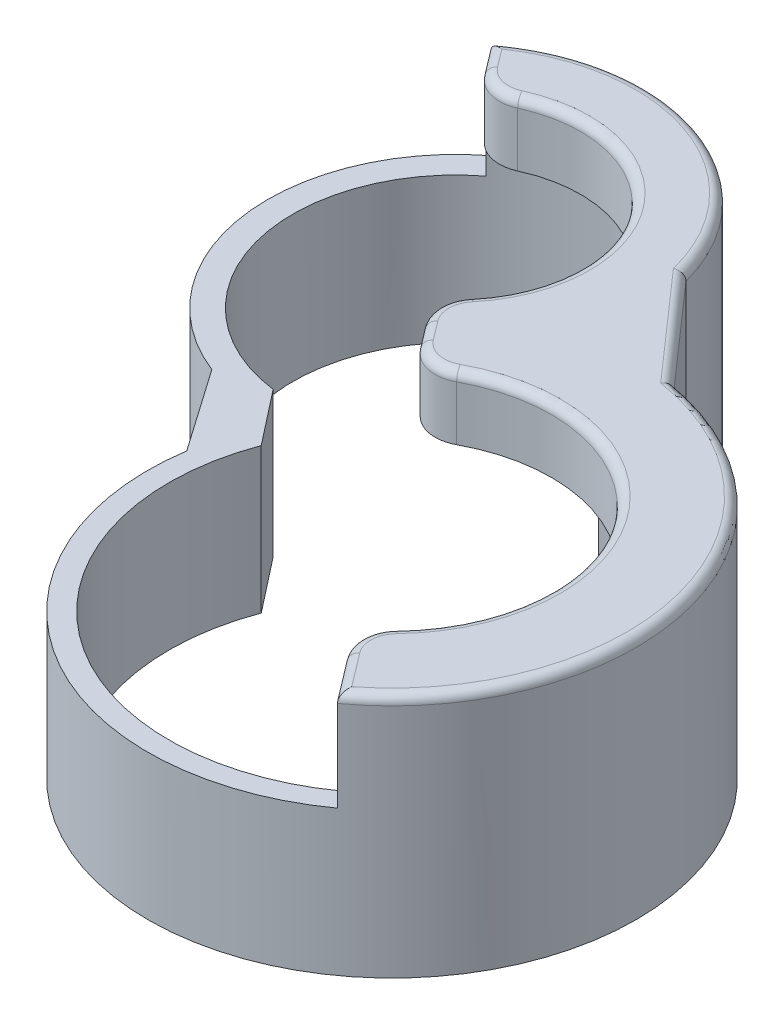
SolidWorks part; units mm, degrees
note: The reader was unsure of these and kept them because the rebuilt part matched: shared geometry of "Sketch1<8>".
ref_plane "Front Plane" through (0, 0, 0) normal (0, 0, 1) x (1, 0, 0)
ref_plane "Top Plane" through (0, 0, 0) normal (0, 1, 0) x (1, 0, 0)
ref_plane "Right Plane" through (0, 0, 0) normal (1, 0, 0) x (0, 0, -1)
sketch "Sketch1" plane through (0, 0, 0) normal (0, 1, 0) x (1, 0, 0)
  circle A0 centre (22.4937, 43.6292) radius 8.15
  circle A9 centre (35.203, 27.3848) radius 11.45
  circle A10 centre (35.203, 27.3848) radius 12.3
  circle A16 centre (22.4937, 43.6292) radius 9
  circle A20 centre (22.4937, 43.6292) radius 5
  circle A21 centre (35.203, 27.3848) radius 5
  dimension "D1" = 16.3
  dimension "D6" = 22.9
  dimension "D7" = 24.6
  dimension "D12" = 18
extrude "Boss-Extrude4" add sketch "Sketch1" along normal blind 59 contours A10 A16 | A10 A16 A0 | A16 A10 A9
extrude "Boss-Extrude17" add sketch "Sketch1<8>" along normal blind 10 draft 1
sketch "Sketch1<8>" plane through (0, 0, 0) normal (0, 1, 0) x (1, 0, 0) same geometry as "Sketch1"
sketch "Sketch12" plane through (0, 0, 0) normal (0, -1, 0) x (-1, 0, 0)
  line L1 (-34.9775, 38.8326) -> (-30.6051, 44.4212)
  line L2 (-24.3049, 30.8971) -> (-20.5326, 35.7186)
  circle A0 centre (-35.203, 27.3848) radius 3
  circle A1 centre (-22.4937, 43.6292) radius 3
  circle A2 centre (-35.203, 27.3848) radius 11.45 construction
  circle A3 centre (-35.203, 27.3848) radius 5 construction
  circle A4 centre (-22.4937, 43.6292) radius 8.15 construction
  arc A5 (-25.731, 35.2316) -> (-29.8657, 38.4665) centre (-22.4937, 43.6292) ccw construction
  arc A6 (-20.5326, 35.7186) -> (-30.6051, 44.4212) centre (-22.4937, 43.6292) cw
  arc A7 (-34.9775, 38.8326) -> (-24.3049, 30.8971) centre (-35.203, 27.3848) cw
extrude "Boss-Extrude19" add sketch "Sketch12" against normal blind 59 contours A7 L2 A6 L1
sketch "Sketch17" plane through (0, 0, 0) normal (0, -1, 0) x (1, 0, 0)
  line L0 (23.6821, -31.6931) -> (21.3254, -34.7053)
  line L1 (23.6821, -31.6931) -> (21.3254, -34.7053) construction
  circle A0 centre (35.203, -27.3848) radius 12.3
  circle A1 centre (22.4937, -43.6292) radius 9
  circle M6 centre (35.203, -27.3848) radius 11.45
  circle M7 centre (22.4937, -43.6292) radius 8.15
extrude "Boss-Extrude20" add sketch "Sketch17" against normal blind 3 contours M6 | M7
sketch "Sketch19" plane through (0, 0, 0) normal (0, -1, 0) x (-1, 0, 0)
  circle A0 centre (-35.203, 27.3848) radius 3.2
  circle A1 centre (-22.4937, 43.6292) radius 3.2
  arc A2 (-34.3348, 39.6541) -> (-23.6821, 31.6931) centre (-35.203, 27.3848) ccw construction
  arc A3 (-21.3254, 34.7053) -> (-31.4874, 43.2935) centre (-22.4937, 43.6292) ccw construction
extrude "Cut-Extrude5" cut sketch "Sketch19" against normal blind 10 contours A0 | A1
sketch "Sketch21" plane through (0, 59, 0) normal (0, 1, 0) x (1, 0, 0)
  line L0 (22.4937, 43.6292) -> (35.203, 27.3848) construction
  line L1 (35.203, 27.3848) -> (42.5661, 17.5322) construction
  line L2 (42.5661, 17.5322) -> (17.0125, 50.7675) construction
  line L3 (17.0125, 50.7675) -> (42.5661, 17.5322)
  arc A0 (23.6821, 31.6931) -> (34.3348, 39.6541) centre (35.203, 27.3848) ccw construction
  arc A1 (31.4874, 43.2935) -> (21.3254, 34.7053) centre (22.4937, 43.6292) ccw construction
  circle A2 centre (22.4937, 43.6292) radius 5.0208
  circle A3 centre (35.203, 27.3848) radius 8.7909
sketch "Sketch23" plane through (0, 59, 0) normal (0, 1, 0) x (1, 0, 0)
  line L0 (32.547, 46.256) -> (37.4683, 40.6622)
  line L1 (21.8828, 29.3833) -> (18.69, 33.9596)
  circle A0 centre (35.203, 27.3848) radius 13.4692
  circle A1 centre (22.4937, 43.6292) radius 10.3908
  point P8 (0, 0)
  point P9 (21.8828, 29.3833)
  point P10 (18.69, 33.9596)
  point P11 (0, 0)
  line M5 (21.3254, 34.7053) -> (23.6821, 31.6931)
  arc M6 (23.6821, 31.6931) -> (34.3348, 39.6541) centre (35.203, 27.3848) ccw
  line M7 (34.3348, 39.6541) -> (31.4874, 43.2935)
  arc M8 (31.4874, 43.2935) -> (21.3254, 34.7053) centre (22.4937, 43.6292) ccw
extrude "Boss-Extrude21" add sketch "Sketch23" along normal blind 10 separate body contours A1 L1 A0 M5 | A1 M7 M5 M8 | A1 A0 L0 M7 | A0 M7 M6 M5
sketch "Sketch24" plane through (0, 69, 0) normal (0, 1, 0) x (1, 0, 0)
  line L0 (34.0133, 36.0949) -> (28.919, 41.1893)
  line L1 (18.309, 49.0813) -> (16.1671, 51.8719)
  line L2 (17.0125, 50.7675) -> (42.5661, 17.5322) construction
  line L3 (40.427, 20.3144) -> (43.0995, 16.4731)
  circle A0 centre (22.4937, 43.6292) radius 6.8729
  circle A1 centre (35.203, 27.3848) radius 0.1682
  circle A2 centre (35.203, 27.3848) radius 8.7909
  arc A3 (32.547, 46.256) -> (18.69, 33.9596) centre (22.4937, 43.6292) ccw construction
  arc A4 (21.8828, 29.3833) -> (37.4683, 40.6622) centre (35.203, 27.3848) ccw construction
sketch "Sketch35" plane through (0, 0, 0) normal (0, -1, 0) x (1, 0, 0)
  line L0 (21.3254, -34.7053) -> (23.6821, -31.6931)
  line L1 (34.3348, -39.6541) -> (31.4874, -43.2935)
  arc A0 (23.6821, -31.6931) -> (34.3348, -39.6541) centre (35.203, -27.3848) cw
  arc A1 (31.4874, -43.2935) -> (21.3254, -34.7053) centre (22.4937, -43.6292) cw
extrude "Cut-Extrude8" cut sketch "Sketch35" against normal blind 66
sketch "Sketch36" plane through (0, 69, 0) normal (0, 1, 0) x (1, 0, 0)
  line L0 (43.0995, 16.4731) -> (16.1671, 51.8719)
  line L1 (18.69, 33.9596) -> (21.8828, 29.3833)
  arc A0 (16.1671, 51.8719) -> (18.69, 33.9596) centre (22.4937, 43.6292) ccw
  arc A1 (21.8828, 29.3833) -> (43.0995, 16.4731) centre (35.203, 27.3848) ccw
extrude "Cut-Extrude9" cut sketch "Sketch36" against normal blind 2
sketch "Sketch37" plane through (0, 69, 0) normal (0, 1, 0) x (1, 0, 0)
  line L0 (43.0995, 16.4731) -> (16.1671, 51.8719)
  line L1 (32.547, 46.256) -> (37.4683, 40.6622)
  arc A0 (32.547, 46.256) -> (16.5974, 52.185) centre (22.4937, 43.6292) ccw
  arc A1 (32.547, 46.256) -> (16.1671, 51.8719) centre (22.4937, 43.6292) ccw construction
  arc A2 (37.4683, 40.6622) -> (43.0995, 16.4731) centre (35.203, 27.3848) cw
  circle A3 centre (22.4937, 43.6292) radius 6.8729
  circle A4 centre (35.203, 27.3848) radius 8.7909
  line M2 (42.3913, 17.4039) -> (43.0995, 16.4731)
  arc M3 (43.0995, 16.4731) -> (37.4683, 40.6622) centre (35.203, 27.3848) ccw
  line M4 (37.4683, 40.6622) -> (32.547, 46.256)
  arc M5 (32.547, 46.256) -> (16.1671, 51.8719) centre (22.4937, 43.6292) ccw
  line M6 (16.1671, 51.8719) -> (17.0092, 50.765)
  arc M7 (17.0092, 50.765) -> (31.4874, 43.2935) centre (22.4937, 43.6292) cw
  line M8 (31.4874, 43.2935) -> (34.3348, 39.6541)
  arc M9 (34.3348, 39.6541) -> (42.3913, 17.4039) centre (35.203, 27.3848) cw
extrude "Boss-Extrude24" add sketch "Sketch37" along normal blind 3.5 contours M9 M2 M3 M4 M5 M6 M7 M8 | A4 L0 A3 M9 M8 M7
fillet "Fillet1" radius 2 4 edges at (40.2655, 70.75, -20.1979) (29.6268, 70.75, -34.181) (26.6201, 70.75, -38.1328) (18.2972, 70.75, -49.0722)
fillet "Fillet2" radius 0.5 12 edges at (29.6605, 72.5, -34.9292) (28.0954, 72.5, -36.1939) (27.2913, 72.5, -37.9735) (27.9635, 72.5, -47.7908) (18.3226, 72.5, -49.7616) (16.6926, 72.5, -51.1811) (48.3214, 72.5, -30.4388) (25.8637, 72.5, -53.4583) (35.0077, 72.5, -43.4591) (42.2501, 72.5, -17.5895) (40.9956, 72.5, -20.0308) (42.1992, 72.5, -32.7077)
